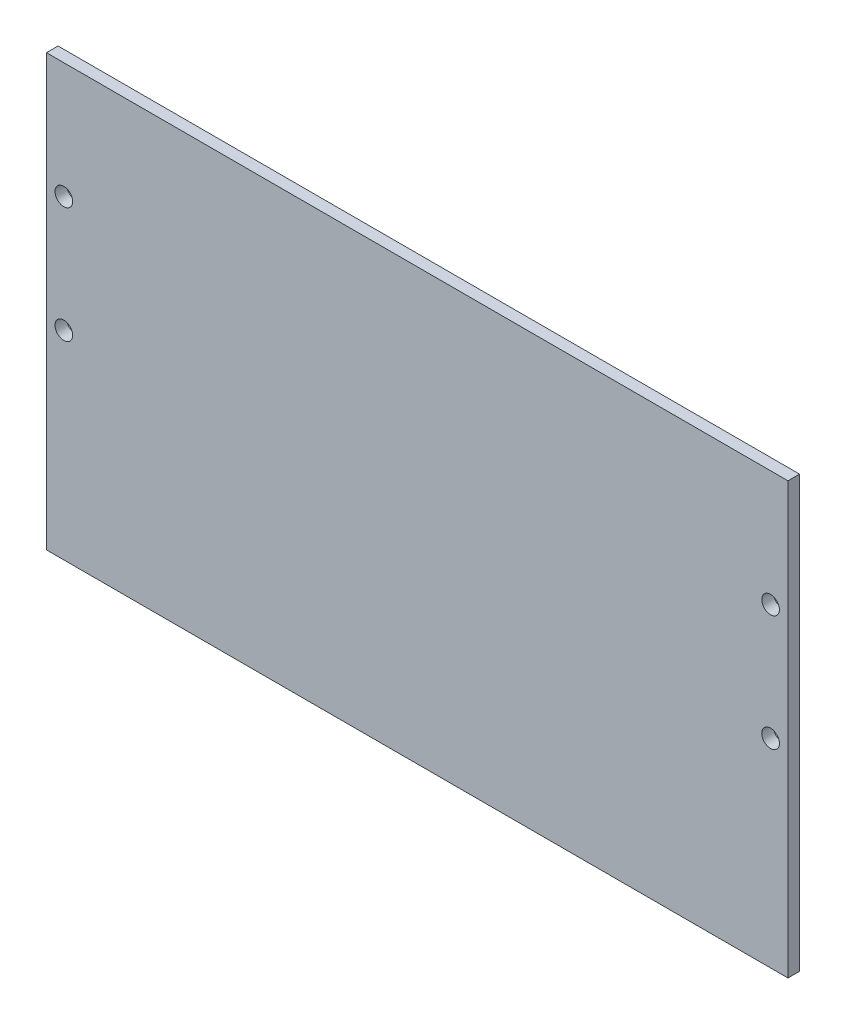
SolidWorks part; units mm, degrees
material "Thornel Mat VMA"
ref_plane "前视基准面" through (0, 0, 0) normal (0, 0, 1) x (1, 0, 0)
ref_plane "上视基准面" through (0, 0, 0) normal (0, 1, 0) x (1, 0, 0)
ref_plane "右视基准面" through (0, 0, 0) normal (1, 0, 0) x (0, 0, -1)
sketch "草图1" plane through (0, 0, 0) normal (0, 0, 1) x (1, 0, 0)
  line L0 (0, 74.3303) -> (-23.5435, 8.4084) construction
  line L1 (0, 0) -> (128, 0)
  line L2 (0, 0) -> (0, 74.3303)
  line L3 (0, 74.3303) -> (128, 74.3303)
  line L4 (128, 0) -> (128, 74.3303)
  line L5 (-23.5435, 8.4084) -> (0, 0) construction
  line L6 (3, 74.3303) -> (3, 54.3303) construction
  line L7 (3, 54.3303) -> (3, 34.3303) construction
  line L8 (64, 74.3303) -> (64, 202.3303) construction
  circle A0 centre (3, 54.3303) radius 1.525
  circle A1 centre (3, 34.3303) radius 1.525
  circle A2 centre (125, 34.3303) radius 1.525
  circle A3 centre (125, 54.3303) radius 1.525
  dimension "D7" = 3.05
  dimension "D1" = 70
  dimension "D2" = 25
  dimension "D3" = 128
  dimension "D4" = 3
  dimension "D5" = 20
  dimension "D6" = 20
extrude "凸台-拉伸1" add sketch "草图1" along normal blind 2
